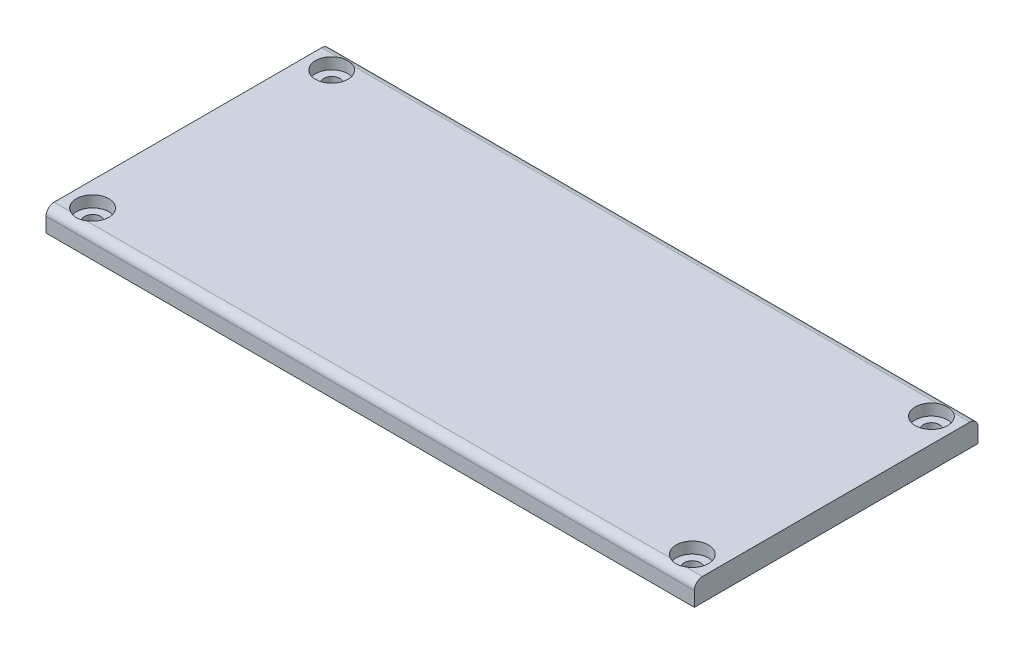
SolidWorks part; units mm, degrees
ref_plane "前视基准面" through (0, 0, 0) normal (0, 0, 1) x (1, 0, 0)
ref_plane "上视基准面" through (0, 0, 0) normal (0, 1, 0) x (1, 0, 0)
ref_plane "右视基准面" through (0, 0, 0) normal (1, 0, 0) x (0, 0, -1)
sketch "草图1" plane through (0, 0, 0) normal (0, 1, 0) x (1, 0, 0)
  line L1 (-21.1046, 6.9952) -> (18.8954, 6.9952)
  line L2 (-21.1046, 6.9952) -> (-21.1046, -10.5048)
  line L3 (-21.1046, -10.5048) -> (18.8954, -10.5048)
  line L4 (18.8954, 6.9952) -> (18.8954, -10.5048)
  dimension "D1" = 17.5
  dimension "D2" = 40
extrude "凸台-拉伸1" add sketch "草图1" along normal blind 1.4
ref_plane "基准面1" through (0, 1.4, 0) normal (0, 1, 0) x (1, 0, 0)
sketch "草图3" plane through (0, 1.4, 0) normal (0, 1, 0) x (1, 0, 0)
  line L0 (18.8954, 6.9952) -> (-21.1046, 6.9952) construction
  line L1 (-21.1046, 6.9952) -> (-21.1046, -10.5048) construction
  circle A0 centre (-19.6046, 5.6202) radius 1
  dimension "D1" = 1.375
  dimension "D2" = 1.5
extrude "切除-拉伸2" cut sketch "草图3" against normal blind 0.7
sketch "草图4" plane through (0, 0.7, 0) normal (0, 1, 0) x (1, 0, 0)
  circle A0 centre (-19.6046, 5.6202) radius 0.5
extrude "切除-拉伸3" cut sketch "草图4" against normal blind 1.5
sketch "草图6" plane through (0, 1.4, 0) normal (0, 1, 0) x (1, 0, 0)
  line L0 (-1.1046, -9.1483) -> (-1.1046, 4.9752) construction
  line L1 (-14.8247, -1.7548) -> (5.1332, -1.7548) construction
  line L2 (-21.1046, 6.9952) -> (-21.1046, -10.5048) construction
  line L3 (18.8954, 6.9952) -> (-21.1046, 6.9952) construction
  dimension "D1" = 20
  dimension "D2" = 8.75
ref_plane "基准面2" through (0, 0, 1.7548) normal (0, 0, 1) x (1, 0, 0)
ref_plane "基准面3" through (-1.1046, 0, 0) normal (1, 0, 0) x (0, 0, -1)
mirror "镜向1" about plane through (0, 0, 1.7548) normal (0, 0, 1) of "切除-拉伸3", "切除-拉伸2"
mirror "镜向2" about plane through (-1.1046, 0, 0) normal (1, 0, 0) of "镜向1", "切除-拉伸3", "切除-拉伸2"
fillet "圆角2" radius 0.5 1 edges at (-1.1046, 1.4, -6.9952)
fillet "圆角3" radius 0.5 1 edges at (-1.1046, 1.4, 10.5048)
